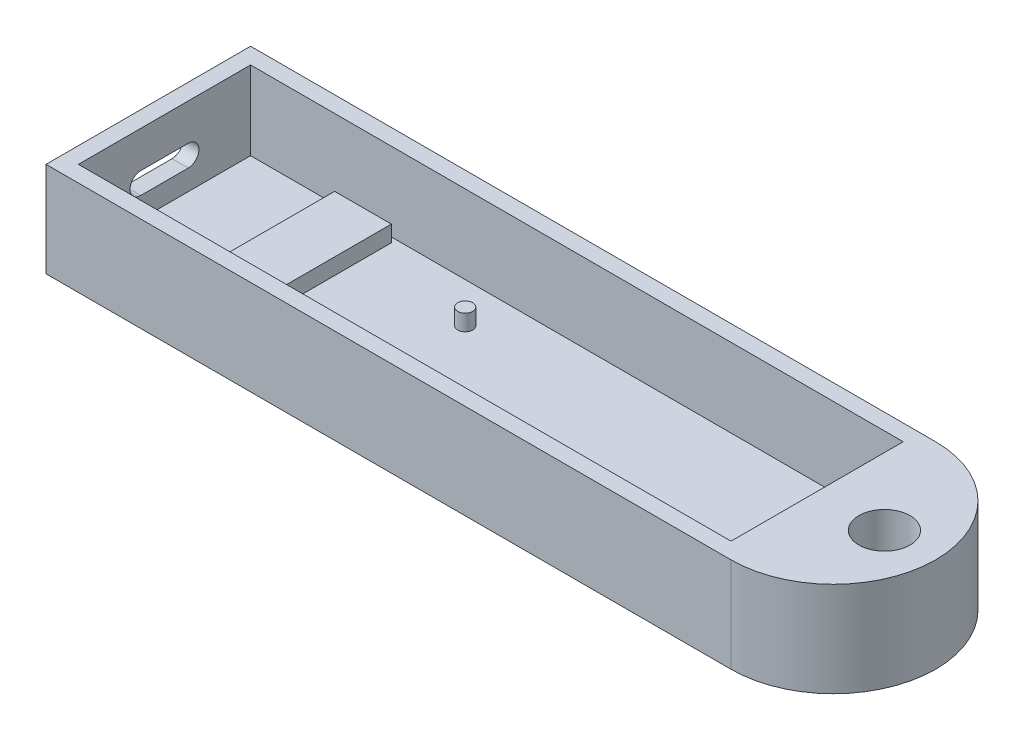
SolidWorks part; units mm, degrees
ref_plane "Front Plane" through (0, 0, 0) normal (0, 0, 1) x (1, 0, 0)
ref_plane "Top Plane" through (0, 0, 0) normal (0, 1, 0) x (1, 0, 0)
ref_plane "Right Plane" through (0, 0, 0) normal (1, 0, 0) x (0, 0, -1)
sketch "Sketch1" plane through (0, 0, 0) normal (0, 1, 0) x (1, 0, 0)
  line L1 (-50.2599, 12.5002) -> (34.2901, 12.5002)
  line L2 (-50.2599, 12.5002) -> (-50.2599, -12.7498)
  line L3 (-50.2599, -12.7498) -> (34.2901, -12.7498)
  line L4 (34.2901, 12.5002) -> (34.2901, -12.7498)
  line L5 (-50.2599, 12.5002) -> (34.2901, -12.7498) construction
  line L6 (-50.2599, -12.7498) -> (34.2901, 12.5002) construction
  line L7 (-48.2599, 10.5002) -> (32.2901, 10.5002)
  line L8 (-48.2599, 10.5002) -> (-48.2599, -10.7498)
  line L9 (-48.2599, -10.7498) -> (32.2901, -10.7498)
  line L10 (32.2901, 10.5002) -> (32.2901, -10.7498)
  line L11 (-48.2599, 10.5002) -> (32.2901, -10.7498) construction
  line L12 (-48.2599, -10.7498) -> (32.2901, 10.5002) construction
  line L13 (-37.2599, -10.1248) -> (-30.2599, -10.1248)
  line L14 (-37.2599, -10.1248) -> (-37.2599, 9.8752)
  line L15 (-37.2599, 9.8752) -> (-30.2599, 9.8752)
  line L16 (-30.2599, -10.1248) -> (-30.2599, 9.8752)
  line L17 (-37.2599, -10.1248) -> (-30.2599, 9.8752) construction
  line L18 (-37.2599, 9.8752) -> (-30.2599, -10.1248) construction
  circle A1 centre (34.2901, -0.1248) radius 12.625
  circle A2 centre (40.6001, -0.1248) radius 3.155
  circle A3 centre (-16.8399, 5.5702) radius 0.925
  circle A4 centre (-16.8399, -7.3814) radius 0.925
  circle A5 centre (30.1601, -7.3814) radius 0.925
  circle A6 centre (30.1601, 5.5702) radius 0.925
  point P0 (-7.9849, -0.1248)
  point P5 (-7.9849, -0.1248)
  point P14 (-33.7599, -0.1248)
  point P19 (-48.2599, -0.1248)
  dimension "D5" = 6.31
  dimension "D10" = 1.85
  dimension "D11" = 1.85
  dimension "D12" = 1.85
  dimension "D13" = 1.85
  dimension "D1" = 25.25
  dimension "D2" = 84.55
  dimension "D3" = 80.55
  dimension "D4" = 21.25
  dimension "D6" = 6.31
  dimension "D7" = 7
  dimension "D8" = 20
  dimension "D9" = 11
  dimension "D14" = 49.13
  dimension "D15" = 4.93
  dimension "D16" = 2.13
extrude "Boss-Extrude2" add sketch "Sketch1" along normal blind 4 contours L13 L16 L15 L14 region at (-33.7599, 0, 0.1248)
extrude "Boss-Extrude3" add sketch "Sketch1<4>" along normal blind 2 contours A1 L7 L8 L9 A4 A3 L16 L13 L14 L15 | L7 A1 L9 L10 A6 A5 region at (-10.2353, 0, 0.1218) region at (27.6108, 0, 0.102)
sketch "Sketch1<4>" plane through (0, 0, 0) normal (0, 1, 0) x (1, 0, 0) same geometry as "Sketch1"
extrude "Boss-Extrude4" add sketch "Sketch1<5>" along normal blind 4 contours A3 | A4 | A5 | A6
sketch "Sketch1<5>" plane through (0, 0, 0) normal (0, 1, 0) x (1, 0, 0) same geometry as "Sketch1"
extrude "Boss-Extrude5" add sketch "Sketch1<6>" along normal blind 11.7 contours A1 L1 L2 L3 L9 L8 L7 | L4 A1 L7 L10 L9 | L4 A1 A2 region at (-7.9849, 0, -11.6178) region at (43.0177, 0, -8.6028) region at (32.809, 0, 0.1248)
sketch "Sketch1<6>" plane through (0, 0, 0) normal (0, 1, 0) x (1, 0, 0) same geometry as "Sketch1"
sketch "Sketch3" plane through (-50.2599, 0, 0) normal (-1, 0, 0) x (0, 0, 1)
  line L0 (-2.8002, 5.85) -> (3.0498, 5.85) construction
  line L1 (-2.8002, 7.175) -> (3.0498, 7.175)
  line L2 (-2.8002, 4.525) -> (3.0498, 4.525)
  line L3 (-12.5002, 0) -> (12.7498, 0) construction
  line L4 (-12.5002, 0) -> (12.7498, 0)
  arc A0 (-2.8002, 7.175) -> (-2.8002, 4.525) centre (-2.8002, 5.85) ccw
  arc A1 (3.0498, 4.525) -> (3.0498, 7.175) centre (3.0498, 5.85) ccw
  point P2 (0.1248, 5.85)
  point P7 (-4.1252, 5.85)
  point P8 (4.3748, 5.85)
  point P14 (0.1248, 0)
  dimension "D3" = 8.5
  dimension "D1" = 5.85
  dimension "D2" = 2.65
extrude "Cut-Extrude1" cut sketch "Sketch3" along normal mid plane 9.7 contours L1 A1 L2 A0
